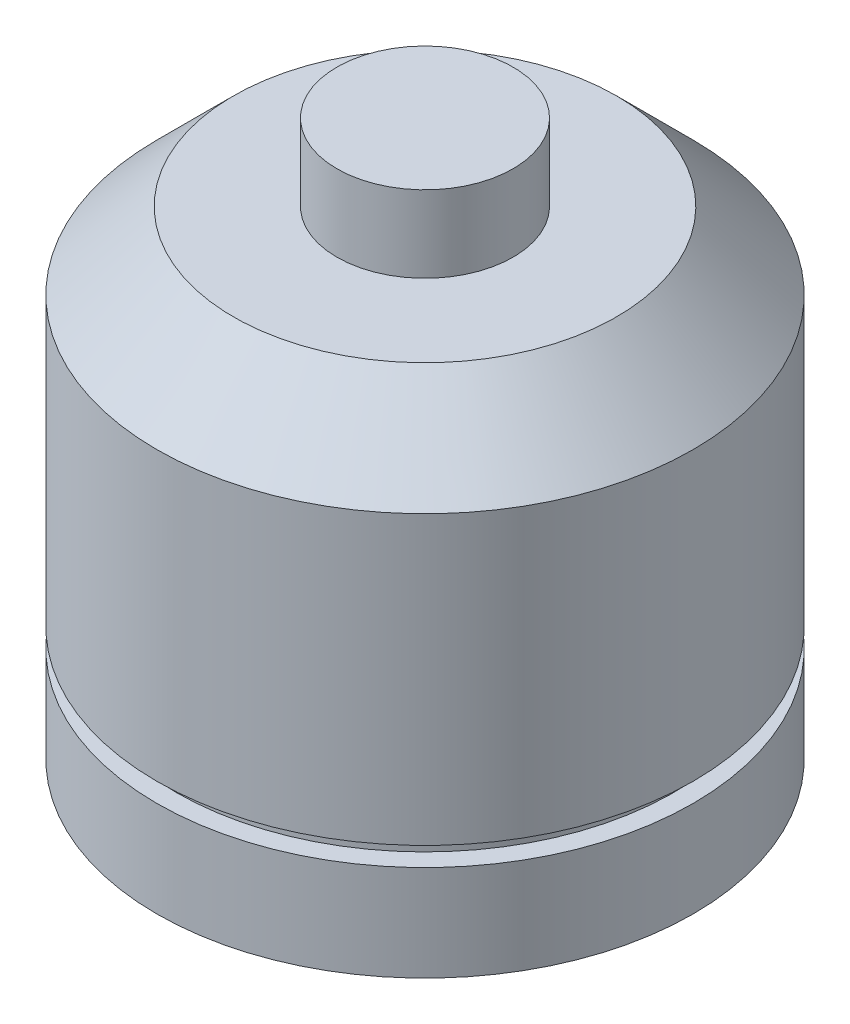
SolidWorks part; units mm, degrees
ref_plane "Front Plane" through (0, 0, 0) normal (0, 0, 1) x (1, 0, 0)
ref_plane "Top Plane" through (0, 0, 0) normal (0, 1, 0) x (1, 0, 0)
ref_plane "Right Plane" through (0, 0, 0) normal (1, 0, 0) x (0, 0, -1)
ref_axis "Axis1" through (0, -14.275, 0) along (0, 1, 0)
sketch "Sketch1" plane through (0, 0, 0) normal (1, 0, 0) x (0, 0, -1)
  line L0 (14, 12.175) -> (4.6, 12.175)
  line L1 (0, 12.175) -> (14, 12.175) construction
  line L2 (0, 12.175) -> (0, -12.825)
  line L3 (0, -12.825) -> (14, -12.825)
  line L4 (14, 12.175) -> (14, -12.825) construction
  line L5 (7, -12.825) -> (7, 12.175) construction
  line L6 (0, -0.325) -> (14, -0.325) construction
  line L7 (4.6, 12.175) -> (4.6, 16.175)
  line L8 (4.6, 16.175) -> (0, 16.175)
  line L9 (0, 16.175) -> (0, 12.175)
  line L10 (14, 12.175) -> (14, -6.825)
  line L11 (14, -6.825) -> (13, -6.825)
  line L12 (13, -6.825) -> (13, -7.825)
  line L13 (13, -7.825) -> (14, -7.825)
  line L14 (14, -7.825) -> (14, -12.825)
  point P0 (7, -0.325)
  dimension "D1" = 4
  dimension "D2" = 4.6
  dimension "D3" = 1
  dimension "D4" = 5
revolve "Revolve1" add sketch "Sketch1" angle 360 about L2
chamfer "Chamfer1" distance 4 angle 45 1 edges at (0, 12.175, 14)
